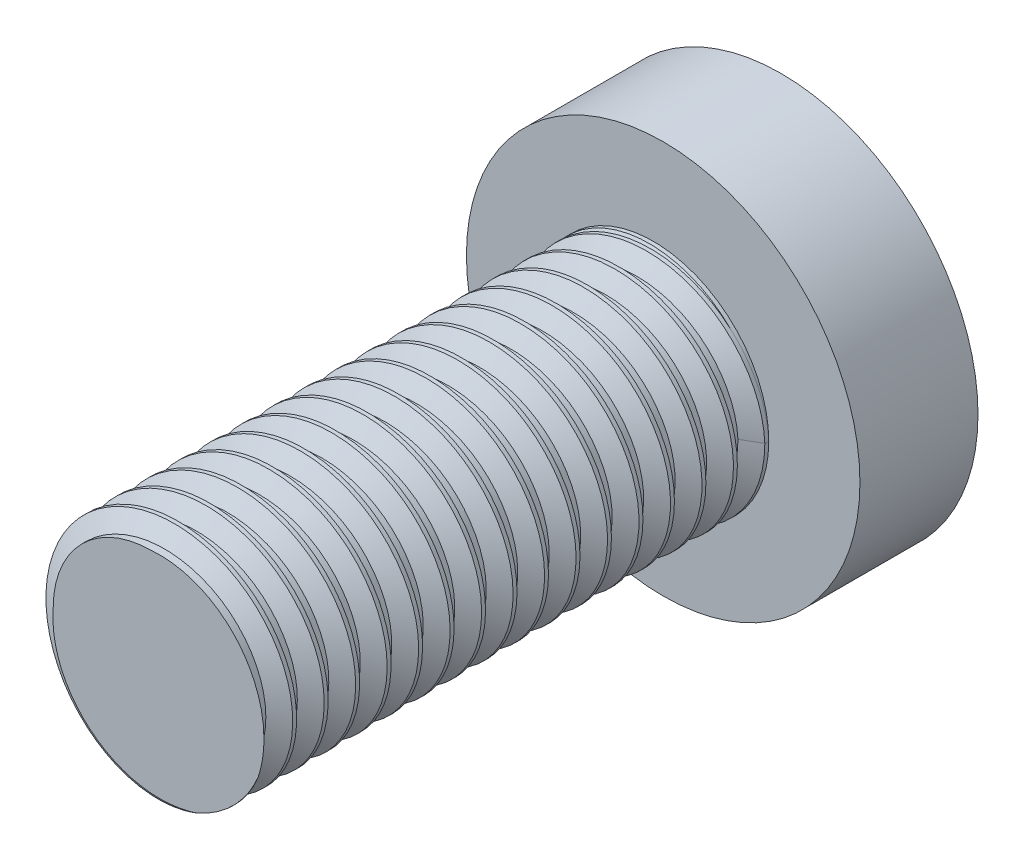
SolidWorks part; units mm, degrees
material "Cast Stainless Steel"
ref_plane "Front Plane" through (0, 0, 0) normal (0, 0, 1) x (1, 0, 0)
ref_plane "Top Plane" through (0, 0, 0) normal (0, 1, 0) x (1, 0, 0)
ref_plane "Right Plane" through (0, 0, 0) normal (1, 0, 0) x (0, 0, -1)
sketch "Sketch1" plane through (0, 0, 0) normal (0, 0, 1) x (1, 0, 0)
  circle A0 centre (0, 0) radius 2.5
  circle A1 centre (0, 0) radius 5
  dimension "D1" = 10
  dimension "D2" = 5
extrude "Boss-Extrude1" add sketch "Sketch1" along normal mid plane 3 contours A1
extrude "Boss-Extrude2" add sketch "Sketch1<3>" along normal blind 14.5 contours A0
sketch "Sketch1<3>" plane through (0, 0, 0) normal (0, 0, 1) x (1, 0, 0) same geometry as "Sketch1"
sketch "Sketch3" plane through (0, 0, -1.5) normal (0, 0, -1) x (-1, 0, 0)
  line L0 (0, 0) -> (0, 3.919) construction
  line L2 (0, 2.8868) -> (-2.5, 1.4434)
  line L3 (-2.5, 1.4434) -> (-2.5, -1.4434)
  line L4 (-2.5, -1.4434) -> (0, -2.8868)
  line L5 (0, -2.8868) -> (2.5, -1.4434)
  line L6 (2.5, -1.4434) -> (2.5, 1.4434)
  line L7 (2.5, 1.4434) -> (0, 2.8868)
  circle A0 centre (0, 0) radius 2.5 construction
  dimension "D1" = 5
extrude "Cut-Extrude1" cut sketch "Sketch3" against normal blind 2.5
thread "Thread1" pitch 0.8 method extrude profile "Thread Profile2" start angle 0, offset 0, length 15, pitch 0.8, diameter 5
ref_plane "Plane2" through (2.5, 0, 1.5) normal (0, -1, 0) x (1, 0, 0)
sketch "Thread Profile2" plane through (2.5, 0, 1.5) normal (0, -1, 0) x (1, 0, 0)
  line L0 (0, 0) -> (0, 0.8) construction
  line L1 (0, 0) -> (0.433, 0.25)
  line L2 (0.433, 0.25) -> (0.433, 0.35)
  line L3 (0.433, 0.35) -> (0, 0.6)
  line L4 (0.433, 0.3) -> (0, 0.3) construction
  line L11 (0, 0) -> (0, 0.6)
  point P2 (0, 0)
  dimension "Pitch" = 0.8
  dimension "Profile_Angle" = 60
  dimension "Profile_Land" = 0.1
  dimension "Profile_Height" = 0.433
sketch "Sketch11" plane through (0, 0, 14.5) normal (0, 0, 1) x (1, 0, 0)
  circle A0 centre (0, 0) radius 5
  dimension "D1" = 10
extrude "Cut-Extrude2" cut sketch "Sketch11" along normal blind 5
sketch "Sketch12" plane through (0, 0, 0) normal (0, -1, 0) x (1, 0, 0)
  line L4 (2.933, 1.75) -> (2.933, 1.85)
  line L5 (2.933, 1.85) -> (2.5, 2.1)
  line L6 (2.5, 2.1) -> (2.5, 1.5)
  line L7 (2.5, 1.5) -> (2.933, 1.75)
  line L8 (2.933, 1.75) -> (2.933, 1.85)
  line L9 (2.933, 1.85) -> (2.5, 2.1)
  line L10 (2.5, 2.1) -> (2.5, 1.5)
  line L11 (2.5, 1.5) -> (2.933, 1.75)
  dimension "D1" = 0
revolve "Revolve1" add sketch "Sketch12" angle 360 about axis through (0, 0, 1.5) along (0, 0, -1)
